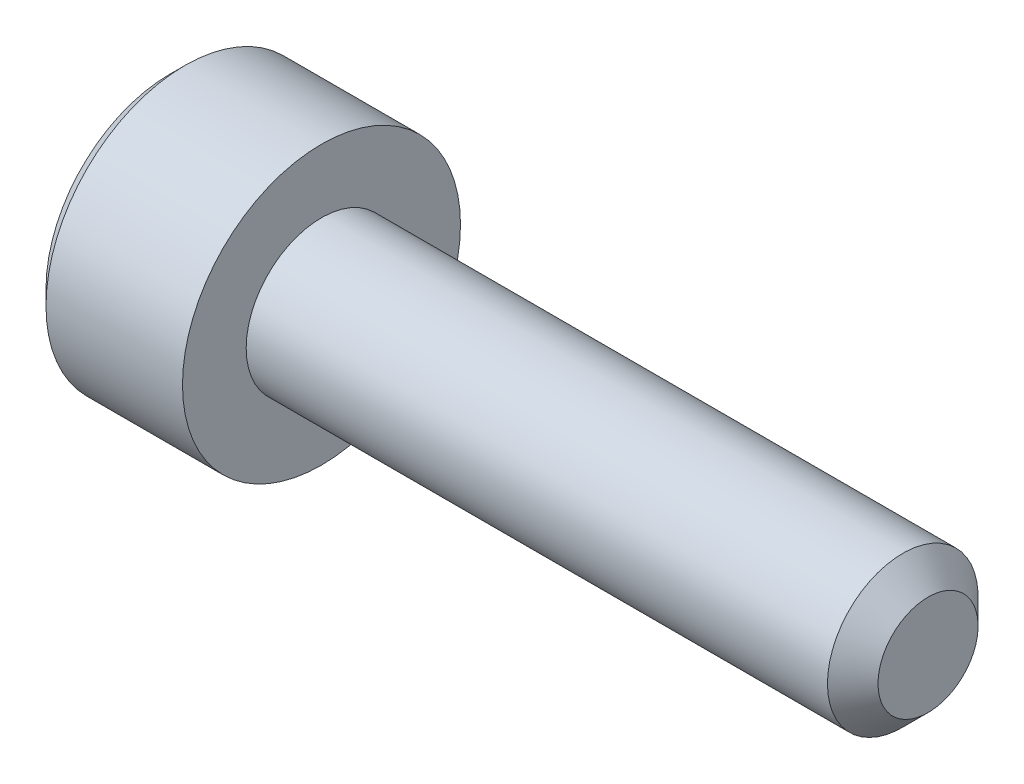
SolidWorks part; units mm, degrees
material "AISI Type 316L stainless steel"
ref_plane "Front Plane" through (0, 0, 0) normal (0, 0, 1) x (1, 0, 0)
ref_plane "Top Plane" through (0, 0, 0) normal (0, 1, 0) x (1, 0, 0)
ref_plane "Right Plane" through (0, 0, 0) normal (1, 0, 0) x (0, 0, -1)
sketch "Sketch1" plane through (0, 0, 0) normal (0, 0, 1) x (1, 0, 0)
  line L0 (-88.7055, 0) -> (96.9812, 0) construction
  line L1 (0, 0) -> (0, 2.75)
  line L2 (0, 2.75) -> (3, 2.75)
  line L4 (15, 0) -> (15, 1.49)
  line L5 (15, 1.49) -> (3, 1.49)
  line L6 (3, 1.49) -> (3, 2.75)
  line L7 (0, 0) -> (15, 0)
  dimension "D1" = 12
  dimension "D2" = 3
  dimension "D3" = 2.75
  dimension "D4" = 1.49
revolve "Revolve1" add sketch "Sketch1" angle 360 about L0
chamfer "Chamfer1" distance 0.5 angle 45 1 edges at (15, 0, 1.49)
chamfer "Chamfer2" distance 0.3 angle 45 1 edges at (0, 0, 2.75)
sketch "Sketch3" plane through (0, 0, 0) normal (1, 0, 0) x (0, 0, -1)
  line L1 (-1.4434, 0) -> (-0.7217, -1.25)
  line L2 (-0.7217, -1.25) -> (0.7217, -1.25)
  line L3 (0.7217, -1.25) -> (1.4434, 0)
  line L4 (1.4434, 0) -> (0.7217, 1.25)
  line L5 (0.7217, 1.25) -> (-0.7217, 1.25)
  line L6 (-0.7217, 1.25) -> (-1.4434, 0)
  circle A0 centre (0, 0) radius 1.25 construction
extrude "Cut-Extrude1" cut sketch "Sketch3" along normal blind 2.5
chamfer "Chamfer3" distance 0.3 angle 45 6 edges at (0, 1.25, 0) (0, 0.625, 1.0825) (0, -0.625, 1.0825) (0, -1.25, 0) (0, -0.625, -1.0825) (0, 0.625, -1.0825)
sketch "Sketch5" plane through (15, 0, 0) normal (1, 0, 0) x (0, 0, -1)
  circle A0 centre (0, 0) radius 1.49
curve "Helix/Spiral1" pitch 0.5 height 20 turns 40
sketch "Sketch8" plane through (0, 0, 0) normal (0, 1, 0) x (1, 0, 0)
  line L0 (15, 1.49) -> (15, 1.1111) construction
  line L1 (15.0625, 1.2194) -> (15.3281, 1.6794)
  line L2 (15.3281, 1.6794) -> (14.6719, 1.6794)
  line L3 (14.6719, 1.6794) -> (14.9375, 1.2194)
  line L4 (15, -0.99) -> (15, 0.99) construction
  circle A0 centre (15, 1.49) radius 0.1894 construction
  arc A1 (15.0625, 1.2194) -> (14.9375, 1.2194) centre (15, 1.2555) cw
  dimension "D2" = 0.0722
  dimension "D1" = 0.3789
sweep "Cut-Sweep1" [suppressed] cut profiles "Sketch8" path "Helix/Spiral1"
equation "\"length\"= 12"
equation "\"D1@Sketch1\"=\"length\""
